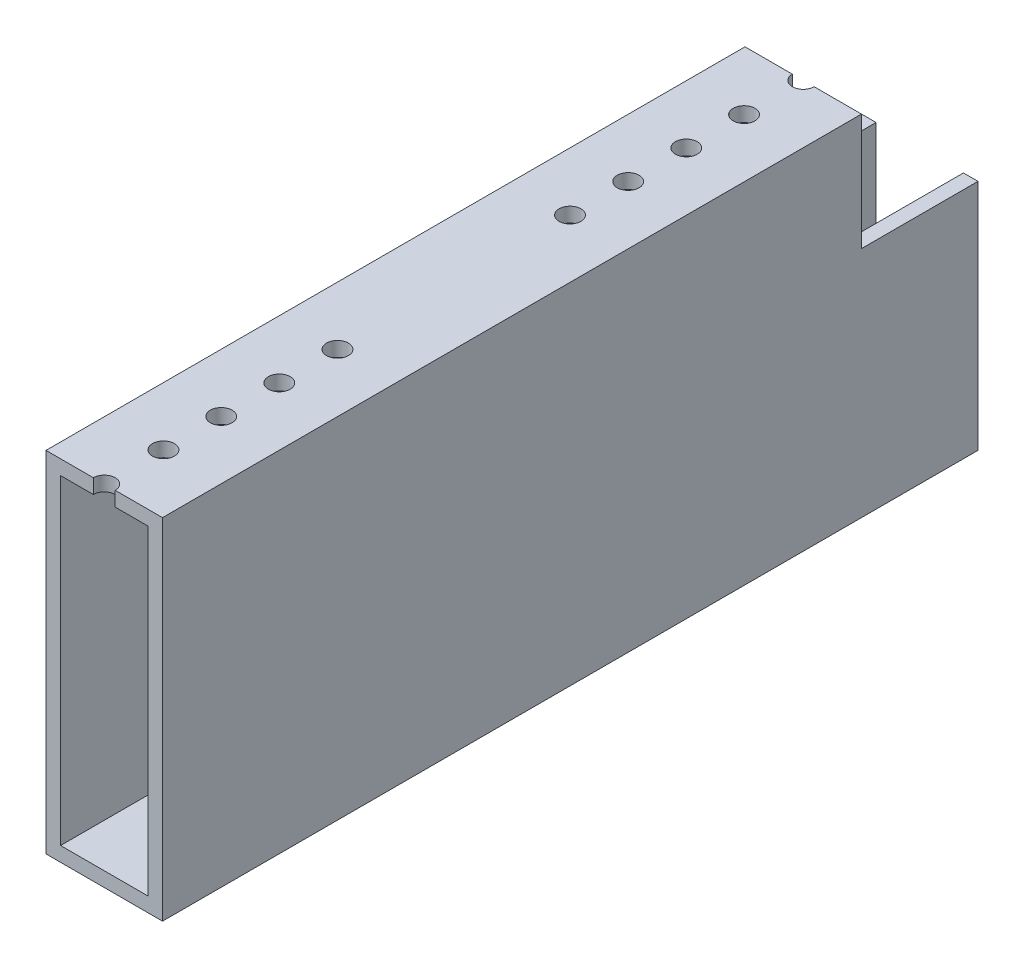
SolidWorks part; units mm, degrees
ref_plane "Front Plane" through (0, 0, 0) normal (0, 0, 1) x (1, 0, 0)
ref_plane "Top Plane" through (0, 0, 0) normal (0, 1, 0) x (1, 0, 0)
ref_plane "Right Plane" through (0, 0, 0) normal (1, 0, 0) x (0, 0, -1)
sketch "Sketch1" plane through (0, 0, 0) normal (0, 0, 1) x (1, 0, 0)
  line L1 (-12.7, -38.1) -> (12.7, -38.1)
  line L2 (-12.7, -38.1) -> (-12.7, 38.1)
  line L3 (-12.7, 38.1) -> (12.7, 38.1)
  line L4 (12.7, -38.1) -> (12.7, 38.1)
  line L5 (-12.7, -38.1) -> (12.7, 38.1) construction
  line L6 (-12.7, 38.1) -> (12.7, -38.1) construction
  point P0 (0, 0)
  dimension "D1" = 25.4
  dimension "D2" = 76.2
extrude "Boss-Extrude1" add sketch "Sketch1" along normal mid plane 177.8
shell "Shell1" thickness 3.175 removed face at (0, 0, -88.9) removed face at (0, 0, 88.9)
sketch "Sketch2" plane through (-12.7, 0, 0) normal (-1, 0, 0) x (0, 0, 1)
  line L1 (-88.9, 38.1) -> (-63.5, 38.1)
  line L2 (-88.9, 38.1) -> (-88.9, 12.7)
  line L3 (-88.9, 12.7) -> (-63.5, 12.7)
  line L4 (-63.5, 38.1) -> (-63.5, 12.7)
  dimension "D1" = 25.4
extrude "Cut-Extrude1" cut sketch "Sketch2" against normal through all
sketch "Sketch3" plane through (0, 38.1, 0) normal (0, 1, 0) x (1, 0, 0)
  line L0 (9.525, -88.9) -> (-9.525, -88.9) construction
  line L1 (12.7, -88.9) -> (-12.7, -88.9) construction
  line L2 (-12.7, -88.9) -> (-12.7, 63.5) construction
  line L3 (-20.8214, -12.7) -> (21.7075, -12.7) construction
  circle A0 centre (0, -88.9) radius 2.3812
  circle A1 centre (0, -75.9959) radius 2.3812
  circle A2 centre (0, -63.3973) radius 2.3812
  circle A3 centre (0, -50.7315) radius 2.3812
  circle A4 centre (0, -38.0486) radius 2.3812
  circle A5 centre (0, 63.5) radius 2.3812
  circle A6 centre (0, 12.6486) radius 2.3812
  circle A7 centre (0, 25.3315) radius 2.3812
  circle A8 centre (0, 37.9973) radius 2.3812
  circle A9 centre (0, 50.5959) radius 2.3812
  point P10 (0, -88.9)
  point P15 (-12.7, -12.7)
  dimension "D1" = 4.7625
  dimension "D3" = 12.9041
  dimension "D2" = 0
  dimension "D4" = 25.5027
  dimension "D5" = 38.1685
  dimension "D6" = 50.8514
extrude "Cut-Extrude2" cut sketch "Sketch3" against normal up to next
sketch "Sketch4" [suppressed] plane through (0, 38.1, 0) normal (0, 1, 0) x (1, 0, 0)
  line L2 (-12.7, -88.9) -> (-12.7, -12.7)
  line L3 (-12.7, -88.9) -> (-12.7, 63.5) construction
  line L4 (-20.5201, -12.7) -> (22.1381, -12.7) construction
